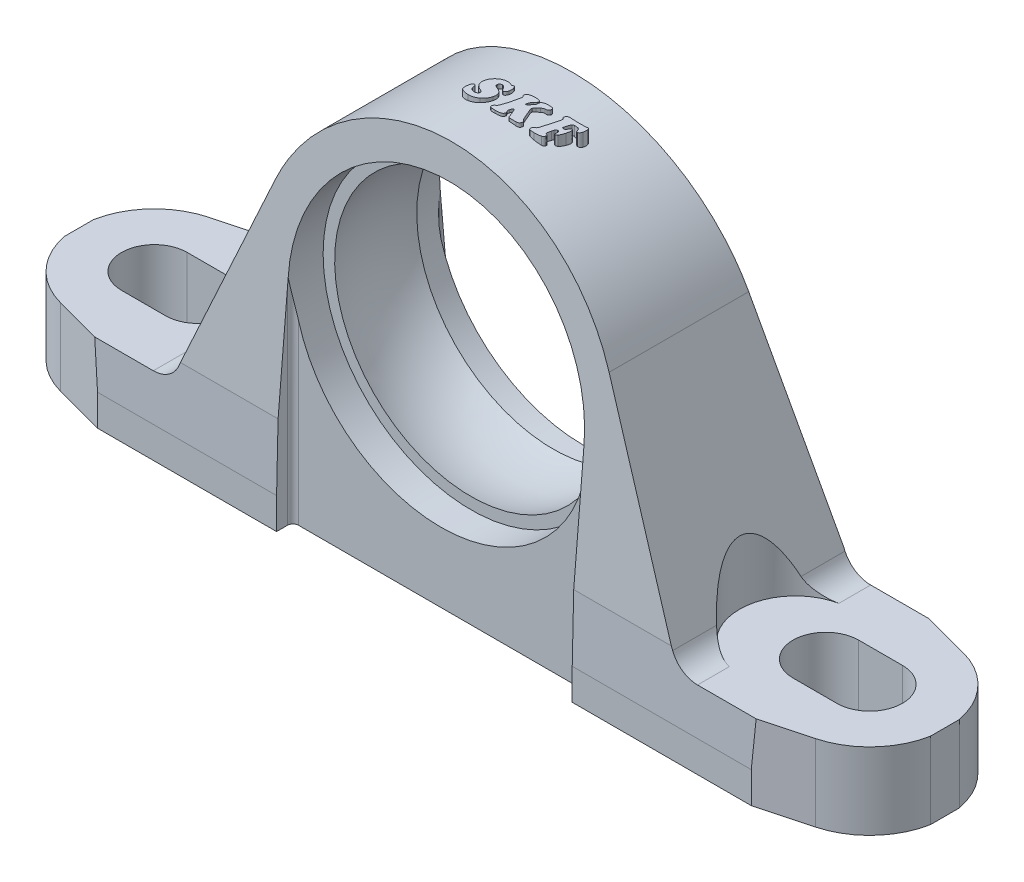
SolidWorks part; units mm, degrees
material "0.6020 (EN-GJL-200)"
ref_plane "Plan de face" through (0, 0, 0) normal (0, 0, 1) x (1, 0, 0)
ref_plane "Plan de dessus" through (0, 0, 0) normal (0, 1, 0) x (1, 0, 0)
ref_plane "Plan de droite" through (0, 0, 0) normal (1, 0, 0) x (0, 0, -1)
sketch "Esquisse1" plane through (0, 0, 0) normal (1, 0, 0) x (0, 0, -1)
  line L0 (-7.5, 27) -> (-7.5, 24.8948)
  line L1 (-16, 33) -> (16, 33)
  line L2 (-8.9054, 0) -> (25.995, 0) construction
  line L3 (-16, 33) -> (-16, 27)
  line L5 (-16, 27) -> (-7.5, 27)
  line L6 (16, 33) -> (16, 27)
  line L7 (7.5, 27) -> (7.5, 24.8948)
  line L8 (7.5, 27) -> (16, 27)
  arc A0 (7.5, 24.8948) -> (-7.5, 24.8948) centre (0, 0) ccw
  dimension "D1" = 52
  dimension "D2" = 15
  dimension "D3" = 7.5
  dimension "D4" = 27
  dimension "D5" = 32
  dimension "D6" = 16
  dimension "D7" = 6
revolve "Révolution1" add sketch "Esquisse1" angle 360 about L2
sketch "Esquisse2" plane through (0, 0, 0) normal (0, 0, 1) x (1, 0, 0)
  line L0 (-30.488, 12.6286) -> (-44.8316, -22)
  line L1 (30.488, 12.6286) -> (44.8316, -22)
  line L2 (-44.8316, -22) -> (-24.5967, -22)
  line L3 (24.5967, -22) -> (44.8316, -22)
  circle A0 centre (0, 0) radius 33 construction
  arc A1 (-30.488, 12.6286) -> (-24.5967, -22) centre (0, 0) ccw
  arc A2 (24.5967, -22) -> (30.488, 12.6286) centre (0, 0) ccw
  dimension "D1" = 45
  dimension "D2" = 22
extrude "Boss.-Extru.1" add sketch "Esquisse2" along normal mid plane 32
sketch "Esquisse3" plane through (0, 0, 0) normal (0, 0, 1) x (1, 0, 0)
  line L0 (-44.8316, -22) -> (-45.0839, -22.6089)
  line L1 (-49.7033, -25.6955) -> (-59.7033, -25.6955)
  line L2 (-59.7033, -25.6955) -> (-59.7033, -34)
  line L3 (-59.7033, -34) -> (59.7033, -34)
  line L4 (59.7033, -34) -> (59.7033, -25.6955)
  line L5 (59.7033, -25.6955) -> (49.7033, -25.6955)
  line L6 (45.0839, -22.6089) -> (44.8316, -22)
  line L7 (44.8316, -22) -> (30.488, 12.6286) construction
  line L8 (-30.488, 12.6286) -> (-44.8316, -22) construction
  line L9 (-44.8316, -22) -> (-24.5967, -22)
  line L10 (24.5967, -22) -> (44.8316, -22)
  arc A0 (-24.5967, -22) -> (24.5967, -22) centre (0, 0) ccw
  arc A1 (49.7033, -25.6955) -> (45.0839, -22.6089) centre (49.7033, -20.6955) cw
  arc A2 (-45.0839, -22.6089) -> (-49.7033, -25.6955) centre (-49.7033, -20.6955) cw
  point P19 (46.3624, -25.6955)
  point P22 (-46.3624, -25.6955)
  dimension "D1" = 34
  dimension "D4" = 5
  dimension "D2" = 4
  dimension "D3" = 4
  dimension "D5" = 10
  dimension "D6" = 10
extrude "Boss.-Extru.2" add sketch "Esquisse3" along normal mid plane 32
sketch "Esquisse4" plane through (0, 0, 0) normal (0, 0, 1) x (1, 0, 0)
  line L0 (-59.7033, -25.6955) -> (-59.7033, -34)
  line L1 (-85, -25.6955) -> (-59.7033, -25.6955)
  line L2 (-85, -25.6955) -> (-85, -39.6955)
  line L3 (-85, -39.6955) -> (85, -39.6955)
  line L4 (85, -25.6955) -> (85, -39.6955)
  line L5 (-59.7033, -34) -> (59.7033, -34)
  line L6 (59.7033, -34) -> (59.7033, -25.6955)
  line L7 (59.7033, -25.6955) -> (85, -25.6955)
  dimension "D1" = 170
  dimension "D2" = 85
  dimension "D3" = 14
extrude "Boss.-Extru.3" add sketch "Esquisse4" along normal mid plane 32
sketch "Esquisse6" plane through (0, -25.6955, 0) normal (0, 1, 0) x (1, 0, 0)
  line L0 (-59.7033, 16) -> (-68.9477, 13.523)
  line L1 (-49.7033, 16) -> (-85, 16) construction
  line L2 (-59.7033, -16) -> (-68.9477, -13.523)
  line L3 (-49.7033, -16) -> (-85, -16) construction
  line L4 (-59.7033, 16) -> (-85, 16)
  line L5 (-85, 16) -> (-85, -16)
  line L6 (-85, -16) -> (-59.7033, -16)
  line L7 (0, 0) -> (0, 22.5138) construction
  line L8 (85, -16) -> (59.7033, -16)
  line L9 (85, 16) -> (85, -16)
  line L10 (59.7033, 16) -> (85, 16)
  line L11 (59.7033, -16) -> (68.9477, -13.523)
  line L12 (59.7033, 16) -> (68.9477, 13.523)
  line L13 (-79.0742, 2.6339) -> (-79.0742, -2.6339)
  line L14 (79.0742, 2.6339) -> (79.0742, -2.6339)
  arc A0 (-68.9477, 13.523) -> (-79.0742, 2.6339) centre (-65.3242, 0) ccw
  arc A1 (68.9477, 13.523) -> (79.0742, 2.6339) centre (65.3242, 0) cw
  arc A2 (-79.0742, -2.6339) -> (-68.9477, -13.523) centre (-65.3242, 0) ccw
  arc A3 (79.0742, -2.6339) -> (68.9477, -13.523) centre (65.3242, 0) cw
  dimension "D5" = 14
  dimension "D6" = 13.75
  dimension "D1" = 10
  dimension "D2" = 10
  dimension "D3" = 15
  dimension "D4" = 15
extrude "Enlèv. mat.-Extru.3" cut sketch "Esquisse6" against normal up to next
sketch "Esquisse7" plane through (0, 0, 0) normal (1, 0, 0) x (0, 0, -1)
  line L0 (11, 33) -> (15.7277, -21.9955)
  line L1 (16, 33) -> (-16, 33) construction
  line L2 (15.7277, -21.9955) -> (16, -33.9955)
  line L3 (16, -22.6089) -> (16, 12.6286) construction
  line L4 (16, 12.6286) -> (16, 33) construction
  line L6 (11, 33) -> (16, 33)
  line L7 (16, 33) -> (16, -33.9955)
  line L8 (16, -39.6955) -> (16, -25.6955) construction
  line L9 (0, 0) -> (0, 17.2771) construction
  line L10 (-16, -25.6955) -> (16, -25.6955) construction
  line L11 (-16, 33) -> (-16, -33.9955)
  line L12 (-11, 33) -> (-16, 33)
  line L13 (-15.7277, -21.9955) -> (-16, -33.9955)
  line L14 (-11, 33) -> (-15.7277, -21.9955)
  dimension "D1" = 5
  dimension "D2" = 1.3
  dimension "D3" = 12
  dimension "D4" = 8.3
extrude "Enlèv. mat.-Extru.6" cut sketch "Esquisse7" against normal up to next and the other way up to next
sketch "Esquisse9" plane through (0, -25.6955, 0) normal (0, 1, 0) x (1, 0, 0)
  line L0 (-49.7033, 10) -> (-49.7033, -10)
  line L1 (-49.7033, -15.8116) -> (-49.7033, 15.8116) construction
  line L2 (0, 0) -> (-18.0541, 0) construction
  line L3 (0, 0) -> (0, 20.0494) construction
  line L4 (49.7033, 10) -> (49.7033, -10)
  arc A0 (49.7033, 10) -> (49.7033, -10) centre (51.7779, 0) ccw
  arc A1 (-49.7033, 10) -> (-49.7033, -10) centre (-51.7779, 0) cw
  dimension "D1" = 20
extrude "Enlèv. mat.-Extru.7" cut sketch "Esquisse9" along normal up to next
sketch "Esquisse10" plane through (0, -25.6955, 0) normal (0, 1, 0) x (1, 0, 0)
  line L0 (-65.3242, 0) -> (-57.3242, 0) construction
  line L1 (-65.3242, 6) -> (-57.3242, 6)
  line L2 (-65.3242, -6) -> (-57.3242, -6)
  line L3 (0, 0) -> (0, 20.9505) construction
  line L4 (65.3242, 0) -> (57.3242, 0) construction
  line L5 (65.3242, 6) -> (57.3242, 6)
  line L6 (65.3242, -6) -> (57.3242, -6)
  arc A0 (-65.3242, 6) -> (-65.3242, -6) centre (-65.3242, 0) ccw
  arc A1 (-57.3242, -6) -> (-57.3242, 6) centre (-57.3242, 0) ccw
  arc A2 (65.3242, 6) -> (65.3242, -6) centre (65.3242, 0) cw
  arc A3 (57.3242, -6) -> (57.3242, 6) centre (57.3242, 0) cw
  arc A4 (-68.9477, 13.523) -> (-79.0742, 2.6339) centre (-65.3242, 0) ccw construction
  point P3 (-61.3242, 0)
  point P12 (61.3242, 0)
  dimension "D2" = 8
  dimension "D1" = 12
extrude "Enlèv. mat.-Extru.8" cut sketch "Esquisse10" against normal up to next
sketch "Esquisse11" plane through (0, 0, 16) normal (0, 0, 1) x (1, 0, 0)
  line L0 (-27, 0) -> (-27, -39.6955)
  line L1 (-59.7033, -39.6955) -> (59.7033, -39.6955) construction
  line L2 (-27, -39.6955) -> (27, -39.6955)
  line L3 (27, -39.6955) -> (27, 0)
  arc A0 (15.6588, -21.9955) -> (-15.6588, -21.9955) centre (0, 0) ccw construction
  circle A1 centre (0, 0) radius 27 construction
  arc A2 (-27, 0) -> (27, 0) centre (0, 0) ccw
extrude "Enlèv. mat.-Extru.9" cut sketch "Esquisse11" against normal blind 3
fillet "Congé1" radius 1 2 edges at (-27, -19.8478, 13) (27, -19.8478, 13)
mirror "Symétrie1" about plane through (0, 0, 0) normal (0, 0, 1) of "Congé1", "Enlèv. mat.-Extru.9"
ref_plane "Plan2" through (0, 33.5, 0) normal (0, 1, 0) x (1, 0, 0)
sketch "Esquisse12" plane through (0, 33.5, 0) normal (0, 1, 0) x (1, 0, 0)
  line L0 (-7.5, -2.5) -> (7.5, -2.5) construction
  text T0 "SKF" font "Cooper Black" height in points 24
  dimension "D1" = 15
  dimension "D2" = 7.5
  dimension "D3" = 2.5
extrude "Boss.-Extru.4" add sketch "Esquisse12" against normal up to next
